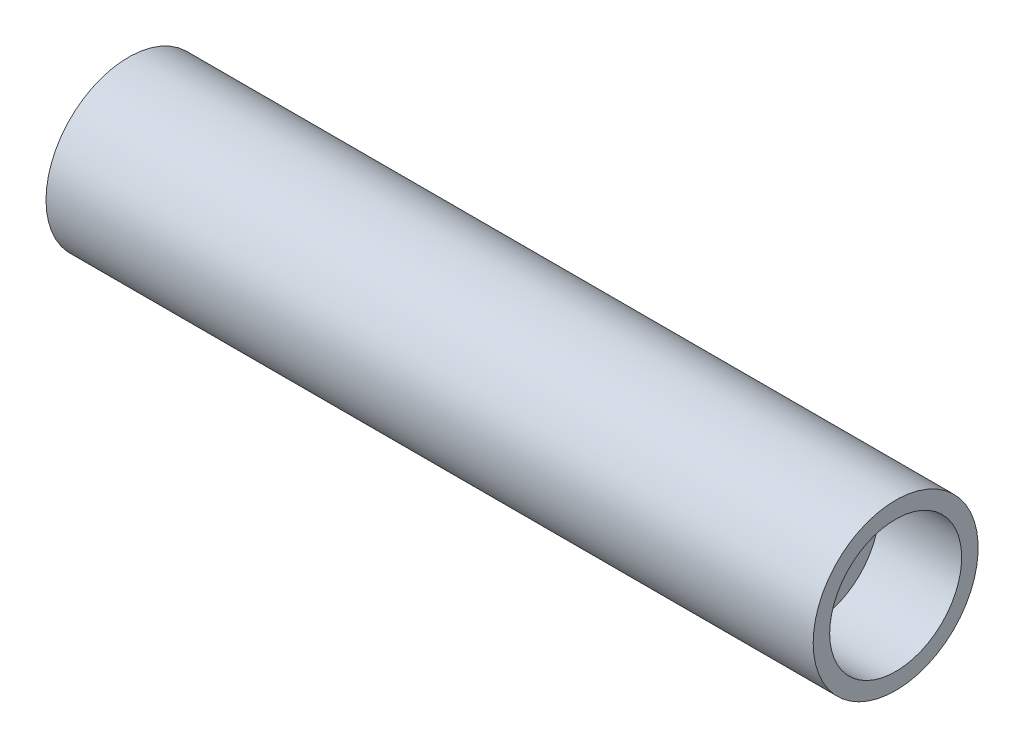
SolidWorks part; units mm, degrees
material "Alloy Steel"
ref_plane "Front Plane" through (0, 0, 0) normal (0, 0, 1) x (1, 0, 0)
ref_plane "Top Plane" through (0, 0, 0) normal (0, 1, 0) x (1, 0, 0)
ref_plane "Right Plane" through (0, 0, 0) normal (1, 0, 0) x (0, 0, -1)
sketch "Sketch2" plane through (0, 0, 0) normal (0, 1, 0) x (1, 0, 0)
  line L0 (0, 5) -> (36.5, 5)
  line L1 (36.5, 5) -> (36.5, 8)
  line L2 (36.5, 8) -> (46.5, 8)
  line L3 (46.5, 8) -> (46.5, 10)
  line L4 (46.5, 10) -> (0, 10)
  line L5 (0, 10) -> (0, 5)
  line L6 (0, 0) -> (64.4269, 0) construction
  line L7 (0, 0) -> (0, 5) construction
  dimension "D1" = 20
  dimension "D2" = 93
  dimension "D3" = 10
  dimension "D4" = 16
  dimension "D5" = 10
revolve "Revolve1" add sketch "Sketch2" angle 360 about L6
mirror "Mirror1" about plane through (0, 0, -10) normal (1, 0, 0) of "Revolve1"
equation "\"D1@Sketch2\"=20mm"
equation "\"D3@Sketch2\"=10mm"
